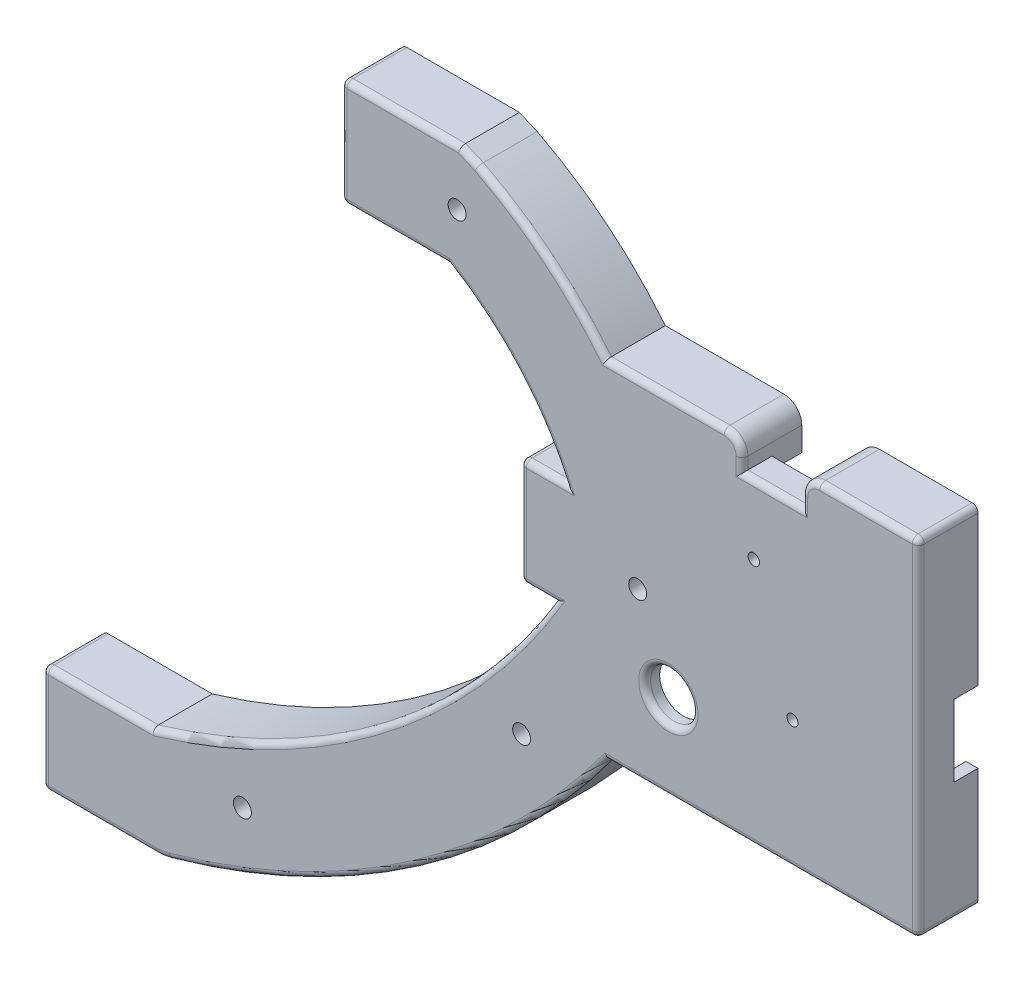
SolidWorks part; units mm, degrees
ref_plane "Front Plane" through (0, 0, 0) normal (0, 0, 1) x (1, 0, 0)
ref_plane "Top Plane" through (0, 0, 0) normal (0, 1, 0) x (1, 0, 0)
ref_plane "Right Plane" through (0, 0, 0) normal (1, 0, 0) x (0, 0, -1)
sketch "Sketch2" plane through (0, 0, 0) normal (0, 0, 1) x (1, 0, 0)
  line L0 (113.097, 105.302) -> (113.097, 100.302)
  line L1 (113.097, 100.302) -> (123.097, 100.302)
  line L2 (123.097, 100.302) -> (123.097, 105.302)
  line L3 (113.097, 105.302) -> (90.2546, 105.302)
  line L26 (-4, -4) -> (15.0023, -4)
  line L27 (90.6538, 47.302) -> (142.597, 47.302)
  line L28 (142.597, 47.302) -> (142.597, 105.302)
  line L29 (142.597, 105.302) -> (90.2546, 105.302)
  line L30 (68.8061, 122.7133) -> (65.8269, 124)
  line L31 (65.8269, 124) -> (46, 124)
  line L32 (46, 124) -> (46, 106)
  line L33 (46, 106) -> (63.9204, 106)
  line L34 (83.571, 84) -> (76, 84)
  line L35 (76, 84) -> (76, 66)
  line L36 (76, 66) -> (81.72, 66)
  line L37 (14.4213, 14) -> (-4, 14)
  line L38 (-4, 14) -> (-4, -4)
  line L39 (-4, -4) -> (15.0023, -4)
  line L40 (90.6538, 47.302) -> (142.597, 47.302)
  line L41 (142.597, 47.302) -> (142.597, 105.302)
  line L42 (142.597, 105.302) -> (123.097, 105.302)
  line L43 (68.8061, 122.7133) -> (65.8269, 124)
  line L44 (65.8269, 124) -> (46, 124)
  line L45 (46, 124) -> (46, 106)
  line L46 (46, 106) -> (63.9204, 106)
  line L47 (83.571, 84) -> (76, 84)
  line L48 (76, 84) -> (76, 66)
  line L49 (76, 66) -> (81.72, 66)
  line L50 (14.4213, 14) -> (-4, 14)
  line L51 (-4, 14) -> (-4, -4)
  circle A0 centre (76.2, 44.069) radius 1.5
  circle A1 centre (95.631, 74.803) radius 1.5
  circle A2 centre (65.405, 114.681) radius 1.5
  circle A3 centre (115.0722, 88.8163) radius 0.9506
  circle A4 centre (121.5373, 68.7604) radius 0.9227
  circle A5 centre (29.464, 10.033) radius 1.5
  circle A6 centre (100.7671, 61.6581) radius 3.9619
  arc A10 (15.0023, -4) -> (17.4339, -3.6649) centre (14.9972, 5.0273) ccw
  arc A11 (17.4339, -3.6649) -> (90.6538, 47.302) centre (-19.3491, 127.2562) ccw
  arc A12 (90.2546, 105.302) -> (68.8061, 122.7133) centre (38.6489, 63.6469) ccw
  arc A13 (83.571, 84) -> (63.9204, 106) centre (38.6559, 63.6576) ccw
  arc A14 (14.4213, 14) -> (81.72, 66) centre (-19.3441, 127.2485) ccw
  arc A15 (15.0023, -4) -> (17.4339, -3.6649) centre (14.9972, 5.0273) ccw
  arc A16 (17.4339, -3.6649) -> (90.6538, 47.302) centre (-19.3491, 127.2562) ccw
  arc A17 (90.2546, 105.302) -> (68.8061, 122.7133) centre (38.6489, 63.6469) ccw
  arc A18 (83.571, 84) -> (63.9204, 106) centre (38.6559, 63.6576) ccw
  arc A19 (14.4213, 14) -> (81.72, 66) centre (-19.3441, 127.2485) ccw
  point P20 (0, 0)
  dimension "D2" = 10
  dimension "D3" = 5
  dimension "D4" = 19.5
  dimension "D1" = 4
extrude "Boss-Extrude1" add sketch "Sketch2" along normal blind 10
sketch "Sketch4" plane through (46, 0, 0) normal (-1, 0, 0) x (0, 0, 1)
  circle A0 centre (0.3059, 115.0899) radius 2.75
  dimension "D1" = 5.5
extrude "Cut-Extrude1" cut sketch "Sketch4" against normal blind 10
sketch "Sketch5" plane through (0, 0, 0) normal (0, 0, -1) x (-1, 0, 0)
  line L82 (-48, 119.9864) -> (-48, 122)
  line L83 (-48, 122) -> (-65.4134, 122)
  line L84 (-65.4134, 122) -> (-67.9535, 120.9029)
  line L85 (-89.2897, 103.302) -> (-111.097, 103.302)
  line L86 (-111.097, 103.302) -> (-111.097, 98.302)
  line L87 (-111.097, 98.302) -> (-125.097, 98.302)
  line L88 (-125.097, 98.302) -> (-125.097, 103.302)
  line L89 (-125.097, 103.302) -> (-140.597, 103.302)
  line L90 (-140.597, 103.302) -> (-140.597, 49.302)
  line L91 (-140.597, 49.302) -> (-89.6303, 49.302)
  line L92 (-15.0023, -2) -> (2, -2)
  line L93 (2, -2) -> (2, 0.6206)
  line L94 (2, 0.6206) -> (-2.012, 0.6206)
  line L95 (-2.012, 0.6206) -> (-2.012, 10.0044)
  line L96 (-2.012, 10.0044) -> (2, 10.0044)
  line L97 (2, 10.0044) -> (2, 12)
  line L98 (2, 12) -> (-14.7119, 12)
  line L99 (-85.2104, 68) -> (-78, 68)
  line L100 (-78, 68) -> (-78, 70.6195)
  line L101 (-78, 70.6195) -> (-81.955, 70.6195)
  line L102 (-81.955, 70.6195) -> (-81.955, 80.0034)
  line L103 (-81.955, 80.0034) -> (-78, 80.0034)
  line L104 (-78, 80.0034) -> (-78, 82)
  line L105 (-78, 82) -> (-86.5721, 82)
  line L106 (-64.4658, 108) -> (-48, 108)
  line L107 (-48, 108) -> (-48, 110.357)
  line L108 (-48, 110.357) -> (-53, 110.357)
  line L109 (-53, 110.357) -> (-53, 119.8229)
  line L110 (-53, 119.8229) -> (-51.923, 119.8229)
  line L111 (-51.923, 119.8229) -> (-51.923, 119.9864)
  line L112 (-51.923, 119.9864) -> (-48, 119.9864)
  line L113 (-48, 119.9864) -> (-48, 122)
  line L114 (-48, 122) -> (-65.4134, 122)
  line L115 (-65.4134, 122) -> (-67.9535, 120.9029)
  line L116 (-89.2897, 103.302) -> (-111.097, 103.302)
  line L117 (-111.097, 103.302) -> (-111.097, 98.302)
  line L118 (-111.097, 98.302) -> (-125.097, 98.302)
  line L119 (-125.097, 98.302) -> (-125.097, 103.302)
  line L120 (-125.097, 103.302) -> (-140.597, 103.302)
  line L121 (-140.597, 103.302) -> (-140.597, 49.302)
  line L122 (-140.597, 49.302) -> (-89.6303, 49.302)
  line L123 (-15.0023, -2) -> (2, -2)
  line L124 (2, -2) -> (2, 0.6206)
  line L125 (2, 0.6206) -> (-2.012, 0.6206)
  line L126 (-2.012, 0.6206) -> (-2.012, 10.0044)
  line L127 (-2.012, 10.0044) -> (2, 10.0044)
  line L128 (2, 10.0044) -> (2, 12)
  line L129 (2, 12) -> (-14.7119, 12)
  line L130 (-85.2104, 68) -> (-78, 68)
  line L131 (-78, 68) -> (-78, 70.6195)
  line L132 (-78, 70.6195) -> (-81.955, 70.6195)
  line L133 (-81.955, 70.6195) -> (-81.955, 80.0034)
  line L134 (-81.955, 80.0034) -> (-78, 80.0034)
  line L135 (-78, 80.0034) -> (-78, 82)
  line L136 (-78, 82) -> (-86.5721, 82)
  line L137 (-64.4658, 108) -> (-48, 108)
  line L138 (-48, 108) -> (-48, 110.357)
  line L139 (-48, 110.357) -> (-53, 110.357)
  line L140 (-53, 110.357) -> (-53, 119.8229)
  line L141 (-53, 119.8229) -> (-51.923, 119.8229)
  line L142 (-51.923, 119.8229) -> (-51.923, 119.9864)
  line L143 (-51.923, 119.9864) -> (-48, 119.9864)
  arc A10 (-67.9535, 120.9029) -> (-89.2897, 103.302) centre (-38.6489, 63.6469) ccw
  arc A11 (-89.6303, 49.302) -> (-16.8941, -1.7391) centre (19.3491, 127.2562) ccw
  arc A12 (-16.8941, -1.7391) -> (-15.0023, -2) centre (-14.9972, 5.0273) ccw
  arc A13 (-85.2104, 68) -> (-14.7119, 12) centre (19.3441, 127.2485) ccw
  arc A14 (-64.4658, 108) -> (-86.5721, 82) centre (-38.6559, 63.6576) ccw
  arc A15 (-67.9535, 120.9029) -> (-89.2897, 103.302) centre (-38.6489, 63.6469) ccw
  arc A16 (-89.6303, 49.302) -> (-16.8941, -1.7391) centre (19.3491, 127.2562) ccw
  arc A17 (-16.8941, -1.7391) -> (-15.0023, -2) centre (-14.9972, 5.0273) ccw
  arc A18 (-85.2104, 68) -> (-14.7119, 12) centre (19.3441, 127.2485) ccw
  arc A19 (-64.4658, 108) -> (-86.5721, 82) centre (-38.6559, 63.6576) ccw
  dimension "D1" = 2
extrude "Cut-Extrude2" cut sketch "Sketch5" against normal blind 7.5
sketch "Sketch6" plane through (76, 0, 0) normal (-1, 0, 0) x (0, 0, 1)
  circle A0 centre (0.3059, 75.1069) radius 2.75
  dimension "D1" = 5.5
extrude "Cut-Extrude3" cut sketch "Sketch6" against normal blind 6
sketch "Sketch7" plane through (-4, 0, 0) normal (-1, 0, 0) x (0, 0, 1)
  circle A0 centre (0.3059, 5.1079) radius 2.75
  dimension "D1" = 5.5
extrude "Cut-Extrude4" cut sketch "Sketch7" against normal blind 16
sketch "Sketch8" plane through (142.597, 0, 0) normal (1, 0, 0) x (0, 0, -1)
  line L0 (0, 47.302) -> (0, 105.302) construction
  line L1 (0, 79.302) -> (-4, 79.302)
  line L2 (0, 79.302) -> (0, 67.302)
  line L3 (0, 67.302) -> (-4, 67.302)
  line L4 (-4, 79.302) -> (-4, 67.302)
  line L5 (-10, 105.302) -> (0, 105.302) construction
  line L6 (-10, 47.302) -> (0, 47.302) construction
  dimension "D1" = 26
  dimension "D2" = 20
  dimension "D3" = 4
extrude "Cut-Extrude5" cut sketch "Sketch8" against normal blind 6
sketch "Sketch9" plane through (0, 100.302, 0) normal (0, 1, 0) x (1, 0, 0)
  line L0 (113.097, 0) -> (123.097, 0)
  line L1 (123.097, 0) -> (123.097, -5)
  line L2 (123.097, -10) -> (123.097, 0) construction
  line L3 (123.097, -5) -> (113.097, -5)
  line L4 (113.097, -10) -> (113.097, 0) construction
  line L5 (113.097, -5) -> (113.097, 0)
  dimension "D1" = 5
extrude "Cut-Extrude6" cut sketch "Sketch9" against normal blind 6
fillet "Fillet1" radius 3 2 edges at (123.097, 105.302, 5) (113.097, 105.302, 5)
fillet "Fillet2" radius 1 2 edges at (142.597, 47.302, 5) (142.597, 105.302, 5)
fillet "Fillet4" radius 1 32 edges at (58.3422, 15.6435, 10) (16.2295, -3.9155, 10) (5.5011, -4, 10) (-4, 5, 10) (5.2107, 14, 10) (52.9107, 33.7361, 10) (78.86, 66, 10) (76, 75, 10) (79.7855, 84, 10) (75.4294, 96.5039, 10) (54.9602, 106, 10) (46, 115, 10) (55.9134, 124, 10) (67.3165, 123.3566, 10) (80.447, 115.1368, 10) (100.1758, 105.302, 10) (112.2183, 104.4233, 10) (118.097, 100.302, 10) (123.9757, 104.4233, 10) (133.847, 105.302, 10) (142.3041, 105.0091, 10) (142.597, 76.302, 10) (142.3041, 47.5949, 10) (116.1254, 47.302, 10) (-4, -4, 5) (-4, 14, 5) (46, 124, 5) (46, 106, 5) (76, 66, 5) (76, 84, 5) (113.097, 101.302, 10) (123.097, 101.302, 10)
fillet "Fillet5" radius 1 1 edges at (76, 75.1069, 3.0559)
fillet "Fillet6" radius 1 3 edges at (104.729, 61.6581, 10) (-4, 5.1079, 3.0559) (46, 115.0899, 3.0559)
sketch "Sketch10" plane through (0, 0, 7.5) normal (0, 0, -1) x (-1, 0, 0)
  circle A0 centre (-95.631, 74.803) radius 3
  circle A1 centre (-95.631, 74.803) radius 1.5
  circle A2 centre (-76.2, 44.069) radius 1.5
  circle A3 centre (-76.2, 44.069) radius 3
  circle A4 centre (-29.464, 10.033) radius 1.5
  circle A5 centre (-29.464, 10.033) radius 3
  circle A6 centre (-65.405, 114.681) radius 3
  circle A7 centre (-65.405, 114.681) radius 1.5
  dimension "D1" = 6
  dimension "D2" = 3
  dimension "D3" = 3
  dimension "D4" = 6
  dimension "D5" = 6
  dimension "D6" = 3
  dimension "D7" = 6
  dimension "D8" = 3
extrude "Boss-Extrude2" add sketch "Sketch10" along normal blind 7
